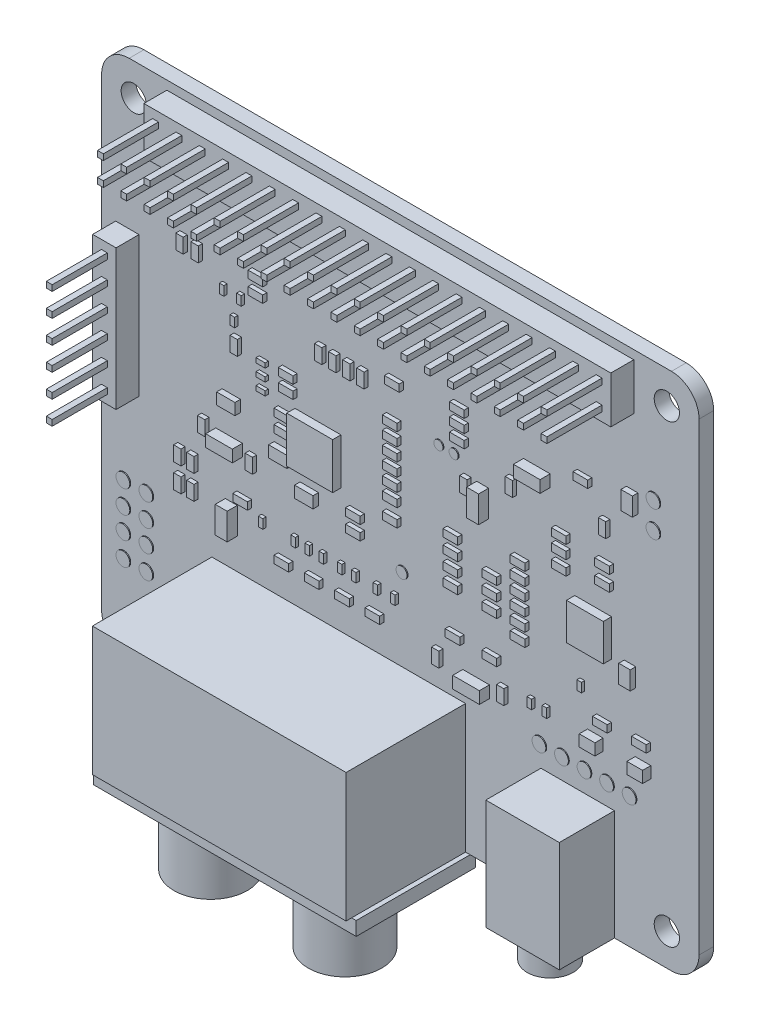
SolidWorks part; units mm, degrees
ref_plane "Front Plane" through (0, 0, 0) normal (0, 0, 1) x (1, 0, 0)
ref_plane "Top Plane" through (0, 0, 0) normal (0, 1, 0) x (1, 0, 0)
ref_plane "Right Plane" through (0, 0, 0) normal (1, 0, 0) x (0, 0, -1)
sketch "Sketch1" plane through (0, 0, 0) normal (0, 0, 1) x (1, 0, 0)
  line L0 (3, 0) -> (62, 0)
  line L1 (65, 3) -> (65, 53.5)
  line L2 (62, 56.5) -> (3, 56.5)
  line L3 (0, 53.5) -> (0, 3)
  arc A0 (62, 0) -> (65, 3) centre (62, 3) ccw
  arc A1 (65, 53.5) -> (62, 56.5) centre (62, 53.5) ccw
  arc A2 (3, 56.5) -> (0, 53.5) centre (3, 53.5) ccw
  arc A3 (0, 3) -> (3, 0) centre (3, 3) ccw
extrude "PCB" add sketch "Sketch1" along normal blind 1.6
ref_plane "Plane_z1_6" through (0, 0, 1.6) normal (0, 0, 1) x (1, 0, 0)
sketch "Sketch2" plane through (0, 0, 1.6) normal (0, 0, 1) x (1, 0, 0)
  line L1 (7.1, 50.46) -> (57.9, 50.46)
  line L2 (7.1, 50.46) -> (7.1, 55.54)
  line L3 (7.1, 55.54) -> (57.9, 55.54)
  line L4 (57.9, 50.46) -> (57.9, 55.54)
  line L6 (1.53, 25.18) -> (4.07, 25.18)
  line L7 (1.53, 25.18) -> (1.53, 40.42)
  line L8 (1.53, 40.42) -> (4.07, 40.42)
  line L9 (4.07, 25.18) -> (4.07, 40.42)
extrude "Header_Blocks" add sketch "Sketch2" along normal blind 2.5
ref_plane "Plane_z4_1" through (0, 0, 4.1) normal (0, 0, 1) x (1, 0, 0)
sketch "Sketch3" plane through (0, 0, 4.1) normal (0, 0, 1) x (1, 0, 0)
  line L1 (8.05, 51.41) -> (8.69, 51.41)
  line L2 (8.05, 51.41) -> (8.05, 52.05)
  line L3 (8.05, 52.05) -> (8.69, 52.05)
  line L4 (8.69, 51.41) -> (8.69, 52.05)
  line L6 (8.05, 53.95) -> (8.69, 53.95)
  line L7 (8.05, 53.95) -> (8.05, 54.59)
  line L8 (8.05, 54.59) -> (8.69, 54.59)
  line L9 (8.69, 53.95) -> (8.69, 54.59)
  line L11 (10.59, 51.41) -> (11.23, 51.41)
  line L12 (10.59, 51.41) -> (10.59, 52.05)
  line L13 (10.59, 52.05) -> (11.23, 52.05)
  line L14 (11.23, 51.41) -> (11.23, 52.05)
  line L16 (10.59, 53.95) -> (11.23, 53.95)
  line L17 (10.59, 53.95) -> (10.59, 54.59)
  line L18 (10.59, 54.59) -> (11.23, 54.59)
  line L19 (11.23, 53.95) -> (11.23, 54.59)
  line L21 (13.13, 51.41) -> (13.77, 51.41)
  line L22 (13.13, 51.41) -> (13.13, 52.05)
  line L23 (13.13, 52.05) -> (13.77, 52.05)
  line L24 (13.77, 51.41) -> (13.77, 52.05)
  line L26 (13.13, 53.95) -> (13.77, 53.95)
  line L27 (13.13, 53.95) -> (13.13, 54.59)
  line L28 (13.13, 54.59) -> (13.77, 54.59)
  line L29 (13.77, 53.95) -> (13.77, 54.59)
  line L31 (15.67, 51.41) -> (16.31, 51.41)
  line L32 (15.67, 51.41) -> (15.67, 52.05)
  line L33 (15.67, 52.05) -> (16.31, 52.05)
  line L34 (16.31, 51.41) -> (16.31, 52.05)
  line L36 (15.67, 53.95) -> (16.31, 53.95)
  line L37 (15.67, 53.95) -> (15.67, 54.59)
  line L38 (15.67, 54.59) -> (16.31, 54.59)
  line L39 (16.31, 53.95) -> (16.31, 54.59)
  line L41 (18.21, 51.41) -> (18.85, 51.41)
  line L42 (18.21, 51.41) -> (18.21, 52.05)
  line L43 (18.21, 52.05) -> (18.85, 52.05)
  line L44 (18.85, 51.41) -> (18.85, 52.05)
  line L46 (18.21, 53.95) -> (18.85, 53.95)
  line L47 (18.21, 53.95) -> (18.21, 54.59)
  line L48 (18.21, 54.59) -> (18.85, 54.59)
  line L49 (18.85, 53.95) -> (18.85, 54.59)
  line L51 (20.75, 51.41) -> (21.39, 51.41)
  line L52 (20.75, 51.41) -> (20.75, 52.05)
  line L53 (20.75, 52.05) -> (21.39, 52.05)
  line L54 (21.39, 51.41) -> (21.39, 52.05)
  line L56 (20.75, 53.95) -> (21.39, 53.95)
  line L57 (20.75, 53.95) -> (20.75, 54.59)
  line L58 (20.75, 54.59) -> (21.39, 54.59)
  line L59 (21.39, 53.95) -> (21.39, 54.59)
  line L61 (23.29, 51.41) -> (23.93, 51.41)
  line L62 (23.29, 51.41) -> (23.29, 52.05)
  line L63 (23.29, 52.05) -> (23.93, 52.05)
  line L64 (23.93, 51.41) -> (23.93, 52.05)
  line L66 (23.29, 53.95) -> (23.93, 53.95)
  line L67 (23.29, 53.95) -> (23.29, 54.59)
  line L68 (23.29, 54.59) -> (23.93, 54.59)
  line L69 (23.93, 53.95) -> (23.93, 54.59)
  line L71 (25.83, 51.41) -> (26.47, 51.41)
  line L72 (25.83, 51.41) -> (25.83, 52.05)
  line L73 (25.83, 52.05) -> (26.47, 52.05)
  line L74 (26.47, 51.41) -> (26.47, 52.05)
  line L76 (25.83, 53.95) -> (26.47, 53.95)
  line L77 (25.83, 53.95) -> (25.83, 54.59)
  line L78 (25.83, 54.59) -> (26.47, 54.59)
  line L79 (26.47, 53.95) -> (26.47, 54.59)
  line L81 (28.37, 51.41) -> (29.01, 51.41)
  line L82 (28.37, 51.41) -> (28.37, 52.05)
  line L83 (28.37, 52.05) -> (29.01, 52.05)
  line L84 (29.01, 51.41) -> (29.01, 52.05)
  line L86 (28.37, 53.95) -> (29.01, 53.95)
  line L87 (28.37, 53.95) -> (28.37, 54.59)
  line L88 (28.37, 54.59) -> (29.01, 54.59)
  line L89 (29.01, 53.95) -> (29.01, 54.59)
  line L91 (30.91, 51.41) -> (31.55, 51.41)
  line L92 (30.91, 51.41) -> (30.91, 52.05)
  line L93 (30.91, 52.05) -> (31.55, 52.05)
  line L94 (31.55, 51.41) -> (31.55, 52.05)
  line L96 (30.91, 53.95) -> (31.55, 53.95)
  line L97 (30.91, 53.95) -> (30.91, 54.59)
  line L98 (30.91, 54.59) -> (31.55, 54.59)
  line L99 (31.55, 53.95) -> (31.55, 54.59)
  line L101 (33.45, 51.41) -> (34.09, 51.41)
  line L102 (33.45, 51.41) -> (33.45, 52.05)
  line L103 (33.45, 52.05) -> (34.09, 52.05)
  line L104 (34.09, 51.41) -> (34.09, 52.05)
  line L106 (33.45, 53.95) -> (34.09, 53.95)
  line L107 (33.45, 53.95) -> (33.45, 54.59)
  line L108 (33.45, 54.59) -> (34.09, 54.59)
  line L109 (34.09, 53.95) -> (34.09, 54.59)
  line L111 (35.99, 51.41) -> (36.63, 51.41)
  line L112 (35.99, 51.41) -> (35.99, 52.05)
  line L113 (35.99, 52.05) -> (36.63, 52.05)
  line L114 (36.63, 51.41) -> (36.63, 52.05)
  line L116 (35.99, 53.95) -> (36.63, 53.95)
  line L117 (35.99, 53.95) -> (35.99, 54.59)
  line L118 (35.99, 54.59) -> (36.63, 54.59)
  line L119 (36.63, 53.95) -> (36.63, 54.59)
  line L121 (38.53, 51.41) -> (39.17, 51.41)
  line L122 (38.53, 51.41) -> (38.53, 52.05)
  line L123 (38.53, 52.05) -> (39.17, 52.05)
  line L124 (39.17, 51.41) -> (39.17, 52.05)
  line L126 (38.53, 53.95) -> (39.17, 53.95)
  line L127 (38.53, 53.95) -> (38.53, 54.59)
  line L128 (38.53, 54.59) -> (39.17, 54.59)
  line L129 (39.17, 53.95) -> (39.17, 54.59)
  line L131 (41.07, 51.41) -> (41.71, 51.41)
  line L132 (41.07, 51.41) -> (41.07, 52.05)
  line L133 (41.07, 52.05) -> (41.71, 52.05)
  line L134 (41.71, 51.41) -> (41.71, 52.05)
  line L136 (41.07, 53.95) -> (41.71, 53.95)
  line L137 (41.07, 53.95) -> (41.07, 54.59)
  line L138 (41.07, 54.59) -> (41.71, 54.59)
  line L139 (41.71, 53.95) -> (41.71, 54.59)
  line L141 (43.61, 51.41) -> (44.25, 51.41)
  line L142 (43.61, 51.41) -> (43.61, 52.05)
  line L143 (43.61, 52.05) -> (44.25, 52.05)
  line L144 (44.25, 51.41) -> (44.25, 52.05)
  line L146 (43.61, 53.95) -> (44.25, 53.95)
  line L147 (43.61, 53.95) -> (43.61, 54.59)
  line L148 (43.61, 54.59) -> (44.25, 54.59)
  line L149 (44.25, 53.95) -> (44.25, 54.59)
  line L151 (46.15, 51.41) -> (46.79, 51.41)
  line L152 (46.15, 51.41) -> (46.15, 52.05)
  line L153 (46.15, 52.05) -> (46.79, 52.05)
  line L154 (46.79, 51.41) -> (46.79, 52.05)
  line L156 (46.15, 53.95) -> (46.79, 53.95)
  line L157 (46.15, 53.95) -> (46.15, 54.59)
  line L158 (46.15, 54.59) -> (46.79, 54.59)
  line L159 (46.79, 53.95) -> (46.79, 54.59)
  line L161 (48.69, 51.41) -> (49.33, 51.41)
  line L162 (48.69, 51.41) -> (48.69, 52.05)
  line L163 (48.69, 52.05) -> (49.33, 52.05)
  line L164 (49.33, 51.41) -> (49.33, 52.05)
  line L166 (48.69, 53.95) -> (49.33, 53.95)
  line L167 (48.69, 53.95) -> (48.69, 54.59)
  line L168 (48.69, 54.59) -> (49.33, 54.59)
  line L169 (49.33, 53.95) -> (49.33, 54.59)
  line L171 (51.23, 51.41) -> (51.87, 51.41)
  line L172 (51.23, 51.41) -> (51.23, 52.05)
  line L173 (51.23, 52.05) -> (51.87, 52.05)
  line L174 (51.87, 51.41) -> (51.87, 52.05)
  line L176 (51.23, 53.95) -> (51.87, 53.95)
  line L177 (51.23, 53.95) -> (51.23, 54.59)
  line L178 (51.23, 54.59) -> (51.87, 54.59)
  line L179 (51.87, 53.95) -> (51.87, 54.59)
  line L181 (53.77, 51.41) -> (54.41, 51.41)
  line L182 (53.77, 51.41) -> (53.77, 52.05)
  line L183 (53.77, 52.05) -> (54.41, 52.05)
  line L184 (54.41, 51.41) -> (54.41, 52.05)
  line L186 (53.77, 53.95) -> (54.41, 53.95)
  line L187 (53.77, 53.95) -> (53.77, 54.59)
  line L188 (53.77, 54.59) -> (54.41, 54.59)
  line L189 (54.41, 53.95) -> (54.41, 54.59)
  line L191 (56.31, 51.41) -> (56.95, 51.41)
  line L192 (56.31, 51.41) -> (56.31, 52.05)
  line L193 (56.31, 52.05) -> (56.95, 52.05)
  line L194 (56.95, 51.41) -> (56.95, 52.05)
  line L196 (56.31, 53.95) -> (56.95, 53.95)
  line L197 (56.31, 53.95) -> (56.31, 54.59)
  line L198 (56.31, 54.59) -> (56.95, 54.59)
  line L199 (56.95, 53.95) -> (56.95, 54.59)
  line L201 (2.48, 26.13) -> (3.12, 26.13)
  line L202 (2.48, 26.13) -> (2.48, 26.77)
  line L203 (2.48, 26.77) -> (3.12, 26.77)
  line L204 (3.12, 26.13) -> (3.12, 26.77)
  line L206 (2.48, 28.67) -> (3.12, 28.67)
  line L207 (2.48, 28.67) -> (2.48, 29.31)
  line L208 (2.48, 29.31) -> (3.12, 29.31)
  line L209 (3.12, 28.67) -> (3.12, 29.31)
  line L211 (2.48, 31.21) -> (3.12, 31.21)
  line L212 (2.48, 31.21) -> (2.48, 31.85)
  line L213 (2.48, 31.85) -> (3.12, 31.85)
  line L214 (3.12, 31.21) -> (3.12, 31.85)
  line L216 (2.48, 33.75) -> (3.12, 33.75)
  line L217 (2.48, 33.75) -> (2.48, 34.39)
  line L218 (2.48, 34.39) -> (3.12, 34.39)
  line L219 (3.12, 33.75) -> (3.12, 34.39)
  line L221 (2.48, 36.29) -> (3.12, 36.29)
  line L222 (2.48, 36.29) -> (2.48, 36.93)
  line L223 (2.48, 36.93) -> (3.12, 36.93)
  line L224 (3.12, 36.29) -> (3.12, 36.93)
  line L226 (2.48, 38.83) -> (3.12, 38.83)
  line L227 (2.48, 38.83) -> (2.48, 39.47)
  line L228 (2.48, 39.47) -> (3.12, 39.47)
  line L229 (3.12, 38.83) -> (3.12, 39.47)
extrude "Header_Pins" add sketch "Sketch3" along normal blind 6
sketch "Sketch4" plane through (0, 0, 1.6) normal (0, 0, 1) x (1, 0, 0)
  line L1 (17.1462, 35.0397) -> (18.1462, 35.0397)
  line L2 (17.1462, 35.0397) -> (17.1462, 35.5397)
  line L3 (17.1462, 35.5397) -> (18.1462, 35.5397)
  line L4 (18.1462, 35.0397) -> (18.1462, 35.5397)
  line L6 (17.1462, 33.7251) -> (18.1462, 33.7251)
  line L7 (17.1462, 33.7251) -> (17.1462, 34.2251)
  line L8 (17.1462, 34.2251) -> (18.1462, 34.2251)
  line L9 (18.1462, 33.7251) -> (18.1462, 34.2251)
  line L11 (17.1462, 32.4104) -> (18.1462, 32.4104)
  line L12 (17.1462, 32.4104) -> (17.1462, 32.9104)
  line L13 (17.1462, 32.9104) -> (18.1462, 32.9104)
  line L14 (18.1462, 32.4104) -> (18.1462, 32.9104)
  line L16 (13.1523, 39.5701) -> (13.6523, 39.5701)
  line L17 (13.1523, 39.5701) -> (13.1523, 40.5701)
  line L18 (13.1523, 40.5701) -> (13.6523, 40.5701)
  line L19 (13.6523, 39.5701) -> (13.6523, 40.5701)
  line L21 (15.0385, 39.5701) -> (15.5385, 39.5701)
  line L22 (15.0385, 39.5701) -> (15.0385, 40.5701)
  line L23 (15.0385, 40.5701) -> (15.5385, 40.5701)
  line L24 (15.5385, 39.5701) -> (15.5385, 40.5701)
  line L26 (14.3312, 37.1799) -> (14.8312, 37.1799)
  line L27 (14.3312, 37.1799) -> (14.3312, 38.1799)
  line L28 (14.3312, 38.1799) -> (14.8312, 38.1799)
  line L29 (14.8312, 37.1799) -> (14.8312, 38.1799)
  line L31 (17.3962, 19.7314) -> (17.8962, 19.7314)
  line L32 (17.3962, 19.7314) -> (17.3962, 20.7314)
  line L33 (17.3962, 20.7314) -> (17.8962, 20.7314)
  line L34 (17.8962, 19.7314) -> (17.8962, 20.7314)
  line L36 (20.9328, 19.7314) -> (21.4328, 19.7314)
  line L37 (20.9328, 19.7314) -> (20.9328, 20.7314)
  line L38 (20.9328, 20.7314) -> (21.4328, 20.7314)
  line L39 (21.4328, 19.7314) -> (21.4328, 20.7314)
  line L41 (22.4653, 19.7314) -> (22.9653, 19.7314)
  line L42 (22.4653, 19.7314) -> (22.4653, 20.7314)
  line L43 (22.4653, 20.7314) -> (22.9653, 20.7314)
  line L44 (22.9653, 19.7314) -> (22.9653, 20.7314)
  line L46 (23.9978, 19.7314) -> (24.4978, 19.7314)
  line L47 (23.9978, 19.7314) -> (23.9978, 20.7314)
  line L48 (23.9978, 20.7314) -> (24.4978, 20.7314)
  line L49 (24.4978, 19.7314) -> (24.4978, 20.7314)
  line L51 (26.0018, 19.7314) -> (26.5018, 19.7314)
  line L52 (26.0018, 19.7314) -> (26.0018, 20.7314)
  line L53 (26.0018, 20.7314) -> (26.5018, 20.7314)
  line L54 (26.5018, 19.7314) -> (26.5018, 20.7314)
  line L56 (27.5343, 19.7314) -> (28.0343, 19.7314)
  line L57 (27.5343, 19.7314) -> (27.5343, 20.7314)
  line L58 (27.5343, 20.7314) -> (28.0343, 20.7314)
  line L59 (28.0343, 19.7314) -> (28.0343, 20.7314)
  line L61 (29.892, 19.7314) -> (30.392, 19.7314)
  line L62 (29.892, 19.7314) -> (29.892, 20.7314)
  line L63 (29.892, 20.7314) -> (30.392, 20.7314)
  line L64 (30.392, 19.7314) -> (30.392, 20.7314)
  line L66 (31.7782, 19.7314) -> (32.2782, 19.7314)
  line L67 (31.7782, 19.7314) -> (31.7782, 20.7314)
  line L68 (31.7782, 20.7314) -> (32.2782, 20.7314)
  line L69 (32.2782, 19.7314) -> (32.2782, 20.7314)
  line L71 (46.6317, 17.3412) -> (47.1317, 17.3412)
  line L72 (46.6317, 17.3412) -> (46.6317, 18.3412)
  line L73 (46.6317, 18.3412) -> (47.1317, 18.3412)
  line L74 (47.1317, 17.3412) -> (47.1317, 18.3412)
  line L76 (48.2821, 17.3412) -> (48.7821, 17.3412)
  line L77 (48.2821, 17.3412) -> (48.2821, 18.3412)
  line L78 (48.2821, 18.3412) -> (48.7821, 18.3412)
  line L79 (48.7821, 17.3412) -> (48.7821, 18.3412)
  line L81 (52.0544, 21.6436) -> (52.5544, 21.6436)
  line L82 (52.0544, 21.6436) -> (52.0544, 22.6436)
  line L83 (52.0544, 22.6436) -> (52.5544, 22.6436)
  line L84 (52.5544, 21.6436) -> (52.5544, 22.6436)
extrude "SMD_h0_35" add sketch "Sketch4" along normal blind 0.35
sketch "Sketch5" plane through (0, 0, 1.6) normal (0, 0, 1) x (1, 0, 0)
  line L1 (23.612, 38.553) -> (24.412, 38.553)
  line L2 (23.612, 38.553) -> (23.612, 40.153)
  line L3 (23.612, 40.153) -> (24.412, 40.153)
  line L4 (24.412, 38.553) -> (24.412, 40.153)
  line L6 (25.1445, 38.553) -> (25.9445, 38.553)
  line L7 (25.1445, 38.553) -> (25.1445, 40.153)
  line L8 (25.1445, 40.153) -> (25.9445, 40.153)
  line L9 (25.9445, 38.553) -> (25.9445, 40.153)
  line L11 (26.677, 38.553) -> (27.477, 38.553)
  line L12 (26.677, 38.553) -> (26.677, 40.153)
  line L13 (26.677, 40.153) -> (27.477, 40.153)
  line L14 (27.477, 38.553) -> (27.477, 40.153)
  line L16 (28.2095, 38.553) -> (29.0095, 38.553)
  line L17 (28.2095, 38.553) -> (28.2095, 40.153)
  line L18 (28.2095, 40.153) -> (29.0095, 40.153)
  line L19 (29.0095, 38.553) -> (29.0095, 40.153)
  line L21 (31.2282, 40.1481) -> (32.8282, 40.1481)
  line L22 (31.2282, 40.1481) -> (31.2282, 40.9481)
  line L23 (31.2282, 40.9481) -> (32.8282, 40.9481)
  line L24 (32.8282, 40.1481) -> (32.8282, 40.9481)
  line L26 (16.3747, 42.6578) -> (17.9747, 42.6578)
  line L27 (16.3747, 42.6578) -> (16.3747, 43.4578)
  line L28 (16.3747, 43.4578) -> (17.9747, 43.4578)
  line L29 (17.9747, 42.6578) -> (17.9747, 43.4578)
  line L31 (16.3747, 41.1042) -> (17.9747, 41.1042)
  line L32 (16.3747, 41.1042) -> (16.3747, 41.9042)
  line L33 (16.3747, 41.9042) -> (17.9747, 41.9042)
  line L34 (17.9747, 41.1042) -> (17.9747, 41.9042)
  line L36 (38.3013, 41.2237) -> (39.9013, 41.2237)
  line L37 (38.3013, 41.2237) -> (38.3013, 42.0237)
  line L38 (38.3013, 42.0237) -> (39.9013, 42.0237)
  line L39 (39.9013, 41.2237) -> (39.9013, 42.0237)
  line L41 (38.3013, 39.7896) -> (39.9013, 39.7896)
  line L42 (38.3013, 39.7896) -> (38.3013, 40.5896)
  line L43 (38.3013, 40.5896) -> (39.9013, 40.5896)
  line L44 (39.9013, 39.7896) -> (39.9013, 40.5896)
  line L46 (38.3013, 38.3555) -> (39.9013, 38.3555)
  line L47 (38.3013, 38.3555) -> (38.3013, 39.1555)
  line L48 (38.3013, 39.1555) -> (39.9013, 39.1555)
  line L49 (39.9013, 38.3555) -> (39.9013, 39.1555)
  line L51 (30.9924, 36.3238) -> (32.5924, 36.3238)
  line L52 (30.9924, 36.3238) -> (30.9924, 37.1238)
  line L53 (30.9924, 37.1238) -> (32.5924, 37.1238)
  line L54 (32.5924, 36.3238) -> (32.5924, 37.1238)
  line L56 (30.9924, 34.8897) -> (32.5924, 34.8897)
  line L57 (30.9924, 34.8897) -> (30.9924, 35.6897)
  line L58 (30.9924, 35.6897) -> (32.5924, 35.6897)
  line L59 (32.5924, 34.8897) -> (32.5924, 35.6897)
  line L61 (30.9924, 33.4555) -> (32.5924, 33.4555)
  line L62 (30.9924, 33.4555) -> (30.9924, 34.2555)
  line L63 (30.9924, 34.2555) -> (32.5924, 34.2555)
  line L64 (32.5924, 33.4555) -> (32.5924, 34.2555)
  line L66 (30.9924, 32.0214) -> (32.5924, 32.0214)
  line L67 (30.9924, 32.0214) -> (30.9924, 32.8214)
  line L68 (30.9924, 32.8214) -> (32.5924, 32.8214)
  line L69 (32.5924, 32.0214) -> (32.5924, 32.8214)
  line L71 (30.9924, 30.5873) -> (32.5924, 30.5873)
  line L72 (30.9924, 30.5873) -> (30.9924, 31.3873)
  line L73 (30.9924, 31.3873) -> (32.5924, 31.3873)
  line L74 (32.5924, 30.5873) -> (32.5924, 31.3873)
  line L76 (30.9924, 29.1532) -> (32.5924, 29.1532)
  line L77 (30.9924, 29.1532) -> (30.9924, 29.9532)
  line L78 (30.9924, 29.9532) -> (32.5924, 29.9532)
  line L79 (32.5924, 29.1532) -> (32.5924, 29.9532)
  line L81 (30.9924, 27.241) -> (32.5924, 27.241)
  line L82 (30.9924, 27.241) -> (30.9924, 28.041)
  line L83 (30.9924, 28.041) -> (32.5924, 28.041)
  line L84 (32.5924, 27.241) -> (32.5924, 28.041)
  line L86 (19.6754, 35.1287) -> (21.2754, 35.1287)
  line L87 (19.6754, 35.1287) -> (19.6754, 35.9287)
  line L88 (19.6754, 35.9287) -> (21.2754, 35.9287)
  line L89 (21.2754, 35.1287) -> (21.2754, 35.9287)
  line L91 (19.6754, 33.6946) -> (21.2754, 33.6946)
  line L92 (19.6754, 33.6946) -> (19.6754, 34.4946)
  line L93 (19.6754, 34.4946) -> (21.2754, 34.4946)
  line L94 (21.2754, 33.6946) -> (21.2754, 34.4946)
  line L96 (19.2039, 31.0653) -> (20.8039, 31.0653)
  line L97 (19.2039, 31.0653) -> (19.2039, 31.8653)
  line L98 (19.2039, 31.8653) -> (20.8039, 31.8653)
  line L99 (20.8039, 31.0653) -> (20.8039, 31.8653)
  line L101 (19.2039, 29.5117) -> (20.8039, 29.5117)
  line L102 (19.2039, 29.5117) -> (19.2039, 30.3117)
  line L103 (19.2039, 30.3117) -> (20.8039, 30.3117)
  line L104 (20.8039, 29.5117) -> (20.8039, 30.3117)
  line L106 (26.9843, 25.5679) -> (28.5843, 25.5679)
  line L107 (26.9843, 25.5679) -> (26.9843, 26.3679)
  line L108 (26.9843, 26.3679) -> (28.5843, 26.3679)
  line L109 (28.5843, 25.5679) -> (28.5843, 26.3679)
  line L111 (26.9843, 24.0143) -> (28.5843, 24.0143)
  line L112 (26.9843, 24.0143) -> (26.9843, 24.8143)
  line L113 (26.9843, 24.8143) -> (28.5843, 24.8143)
  line L114 (28.5843, 24.0143) -> (28.5843, 24.8143)
  line L116 (37.594, 28.9142) -> (39.194, 28.9142)
  line L117 (37.594, 28.9142) -> (37.594, 29.7142)
  line L118 (37.594, 29.7142) -> (39.194, 29.7142)
  line L119 (39.194, 28.9142) -> (39.194, 29.7142)
  line L121 (37.594, 27.3605) -> (39.194, 27.3605)
  line L122 (37.594, 27.3605) -> (37.594, 28.1605)
  line L123 (37.594, 28.1605) -> (39.194, 28.1605)
  line L124 (39.194, 27.3605) -> (39.194, 28.1605)
  line L126 (37.594, 25.8069) -> (39.194, 25.8069)
  line L127 (37.594, 25.8069) -> (37.594, 26.6069)
  line L128 (37.594, 26.6069) -> (39.194, 26.6069)
  line L129 (39.194, 25.8069) -> (39.194, 26.6069)
  line L131 (37.594, 24.2533) -> (39.194, 24.2533)
  line L132 (37.594, 24.2533) -> (37.594, 25.0533)
  line L133 (37.594, 25.0533) -> (39.194, 25.0533)
  line L134 (39.194, 24.2533) -> (39.194, 25.0533)
  line L136 (41.8378, 27.241) -> (43.4378, 27.241)
  line L137 (41.8378, 27.241) -> (41.8378, 28.041)
  line L138 (41.8378, 28.041) -> (43.4378, 28.041)
  line L139 (43.4378, 27.241) -> (43.4378, 28.041)
  line L141 (41.8378, 25.6874) -> (43.4378, 25.6874)
  line L142 (41.8378, 25.6874) -> (41.8378, 26.4874)
  line L143 (41.8378, 26.4874) -> (43.4378, 26.4874)
  line L144 (43.4378, 25.6874) -> (43.4378, 26.4874)
  line L146 (41.8378, 24.1338) -> (43.4378, 24.1338)
  line L147 (41.8378, 24.1338) -> (41.8378, 24.9338)
  line L148 (41.8378, 24.9338) -> (43.4378, 24.9338)
  line L149 (43.4378, 24.1338) -> (43.4378, 24.9338)
  line L151 (44.9028, 30.1093) -> (46.5028, 30.1093)
  line L152 (44.9028, 30.1093) -> (44.9028, 30.9093)
  line L153 (44.9028, 30.9093) -> (46.5028, 30.9093)
  line L154 (46.5028, 30.1093) -> (46.5028, 30.9093)
  line L156 (44.9028, 28.6751) -> (46.5028, 28.6751)
  line L157 (44.9028, 28.6751) -> (44.9028, 29.4751)
  line L158 (44.9028, 29.4751) -> (46.5028, 29.4751)
  line L159 (46.5028, 28.6751) -> (46.5028, 29.4751)
  line L161 (44.9028, 27.241) -> (46.5028, 27.241)
  line L162 (44.9028, 27.241) -> (44.9028, 28.041)
  line L163 (44.9028, 28.041) -> (46.5028, 28.041)
  line L164 (46.5028, 27.241) -> (46.5028, 28.041)
  line L166 (44.9028, 25.8069) -> (46.5028, 25.8069)
  line L167 (44.9028, 25.8069) -> (44.9028, 26.6069)
  line L168 (44.9028, 26.6069) -> (46.5028, 26.6069)
  line L169 (46.5028, 25.8069) -> (46.5028, 26.6069)
  line L171 (44.9028, 24.3728) -> (46.5028, 24.3728)
  line L172 (44.9028, 24.3728) -> (44.9028, 25.1728)
  line L173 (44.9028, 25.1728) -> (46.5028, 25.1728)
  line L174 (46.5028, 24.3728) -> (46.5028, 25.1728)
  line L176 (44.9028, 22.9387) -> (46.5028, 22.9387)
  line L177 (44.9028, 22.9387) -> (44.9028, 23.7387)
  line L178 (44.9028, 23.7387) -> (46.5028, 23.7387)
  line L179 (46.5028, 22.9387) -> (46.5028, 23.7387)
  line L181 (49.3825, 34.8897) -> (50.9825, 34.8897)
  line L182 (49.3825, 34.8897) -> (49.3825, 35.6897)
  line L183 (49.3825, 35.6897) -> (50.9825, 35.6897)
  line L184 (50.9825, 34.8897) -> (50.9825, 35.6897)
  line L186 (49.3825, 33.4555) -> (50.9825, 33.4555)
  line L187 (49.3825, 33.4555) -> (49.3825, 34.2555)
  line L188 (49.3825, 34.2555) -> (50.9825, 34.2555)
  line L189 (50.9825, 33.4555) -> (50.9825, 34.2555)
  line L191 (49.3825, 31.9019) -> (50.9825, 31.9019)
  line L192 (49.3825, 31.9019) -> (49.3825, 32.7019)
  line L193 (49.3825, 32.7019) -> (50.9825, 32.7019)
  line L194 (50.9825, 31.9019) -> (50.9825, 32.7019)
  line L196 (54.4979, 37.5969) -> (55.2979, 37.5969)
  line L197 (54.4979, 37.5969) -> (54.4979, 39.1969)
  line L198 (54.4979, 39.1969) -> (55.2979, 39.1969)
  line L199 (55.2979, 37.5969) -> (55.2979, 39.1969)
  line L201 (54.0979, 34.4116) -> (55.6979, 34.4116)
  line L202 (54.0979, 34.4116) -> (54.0979, 35.2116)
  line L203 (54.0979, 35.2116) -> (55.6979, 35.2116)
  line L204 (55.6979, 34.4116) -> (55.6979, 35.2116)
  line L206 (54.0979, 32.7385) -> (55.6979, 32.7385)
  line L207 (54.0979, 32.7385) -> (54.0979, 33.5385)
  line L208 (54.0979, 33.5385) -> (55.6979, 33.5385)
  line L209 (55.6979, 32.7385) -> (55.6979, 33.5385)
  line L211 (51.7402, 41.3432) -> (53.3402, 41.3432)
  line L212 (51.7402, 41.3432) -> (51.7402, 42.1432)
  line L213 (51.7402, 42.1432) -> (53.3402, 42.1432)
  line L214 (53.3402, 41.3432) -> (53.3402, 42.1432)
  line L216 (39.4086, 34.0116) -> (40.2086, 34.0116)
  line L217 (39.4086, 34.0116) -> (39.4086, 35.6116)
  line L218 (39.4086, 35.6116) -> (40.2086, 35.6116)
  line L219 (40.2086, 34.0116) -> (40.2086, 35.6116)
  line L221 (44.3598, 36.4018) -> (45.1598, 36.4018)
  line L222 (44.3598, 36.4018) -> (44.3598, 38.0018)
  line L223 (44.3598, 38.0018) -> (45.1598, 38.0018)
  line L224 (45.1598, 36.4018) -> (45.1598, 38.0018)
  line L226 (19.2039, 17.2022) -> (20.8039, 17.2022)
  line L227 (19.2039, 17.2022) -> (19.2039, 18.0022)
  line L228 (19.2039, 18.0022) -> (20.8039, 18.0022)
  line L229 (20.8039, 17.2022) -> (20.8039, 18.0022)
  line L231 (22.5047, 17.2022) -> (24.1047, 17.2022)
  line L232 (22.5047, 17.2022) -> (22.5047, 18.0022)
  line L233 (22.5047, 18.0022) -> (24.1047, 18.0022)
  line L234 (24.1047, 17.2022) -> (24.1047, 18.0022)
  line L236 (25.8055, 17.2022) -> (27.4055, 17.2022)
  line L237 (25.8055, 17.2022) -> (25.8055, 18.0022)
  line L238 (25.8055, 18.0022) -> (27.4055, 18.0022)
  line L239 (27.4055, 17.2022) -> (27.4055, 18.0022)
  line L241 (29.1062, 17.2022) -> (30.7062, 17.2022)
  line L242 (29.1062, 17.2022) -> (29.1062, 18.0022)
  line L243 (29.1062, 18.0022) -> (30.7062, 18.0022)
  line L244 (30.7062, 17.2022) -> (30.7062, 18.0022)
  line L246 (8.2869, 21.3436) -> (9.0869, 21.3436)
  line L247 (8.2869, 21.3436) -> (8.2869, 22.9436)
  line L248 (8.2869, 22.9436) -> (9.0869, 22.9436)
  line L249 (9.0869, 21.3436) -> (9.0869, 22.9436)
  line L251 (9.7016, 21.3436) -> (10.5016, 21.3436)
  line L252 (9.7016, 21.3436) -> (9.7016, 22.9436)
  line L253 (9.7016, 22.9436) -> (10.5016, 22.9436)
  line L254 (10.5016, 21.3436) -> (10.5016, 22.9436)
  line L256 (8.2869, 18.7143) -> (9.0869, 18.7143)
  line L257 (8.2869, 18.7143) -> (8.2869, 20.3143)
  line L258 (8.2869, 20.3143) -> (9.0869, 20.3143)
  line L259 (9.0869, 18.7143) -> (9.0869, 20.3143)
  line L261 (9.7016, 18.7143) -> (10.5016, 18.7143)
  line L262 (9.7016, 18.7143) -> (9.7016, 20.3143)
  line L263 (9.7016, 20.3143) -> (10.5016, 20.3143)
  line L264 (10.5016, 18.7143) -> (10.5016, 20.3143)
  line L266 (14.7243, 20.7875) -> (16.3243, 20.7875)
  line L267 (14.7243, 20.7875) -> (14.7243, 21.5875)
  line L268 (14.7243, 21.5875) -> (16.3243, 21.5875)
  line L269 (16.3243, 20.7875) -> (16.3243, 21.5875)
  line L271 (16.0674, 24.4508) -> (16.8673, 24.4508)
  line L272 (16.0674, 24.4508) -> (16.0674, 26.0508)
  line L273 (16.0674, 26.0508) -> (16.8673, 26.0508)
  line L274 (16.8673, 24.4508) -> (16.8673, 26.0508)
  line L276 (10.8804, 25.4069) -> (11.6804, 25.4069)
  line L277 (10.8804, 25.4069) -> (10.8804, 27.0069)
  line L278 (10.8804, 27.0069) -> (11.6804, 27.0069)
  line L279 (11.6804, 25.4069) -> (11.6804, 27.0069)
  line L281 (8.5227, 41.4212) -> (9.3227, 41.4212)
  line L282 (8.5227, 41.4212) -> (8.5227, 43.0212)
  line L283 (8.5227, 43.0212) -> (9.3227, 43.0212)
  line L284 (9.3227, 41.4212) -> (9.3227, 43.0212)
  line L286 (10.1731, 41.4212) -> (10.9731, 41.4212)
  line L287 (10.1731, 41.4212) -> (10.1731, 43.0212)
  line L288 (10.1731, 43.0212) -> (10.9731, 43.0212)
  line L289 (10.9731, 41.4212) -> (10.9731, 43.0212)
  line L291 (14.417, 34.7287) -> (15.217, 34.7287)
  line L292 (14.417, 34.7287) -> (14.417, 36.3287)
  line L293 (14.417, 36.3287) -> (15.217, 36.3287)
  line L294 (15.217, 34.7287) -> (15.217, 36.3287)
  line L296 (41.8378, 19.5924) -> (43.4378, 19.5924)
  line L297 (41.8378, 19.5924) -> (41.8378, 20.3924)
  line L298 (41.8378, 20.3924) -> (43.4378, 20.3924)
  line L299 (43.4378, 19.5924) -> (43.4378, 20.3924)
  line L301 (37.8297, 19.5924) -> (39.4297, 19.5924)
  line L302 (37.8297, 19.5924) -> (37.8297, 20.3924)
  line L303 (37.8297, 20.3924) -> (39.4297, 20.3924)
  line L304 (39.4297, 19.5924) -> (39.4297, 20.3924)
  line L306 (36.3436, 16.3241) -> (37.1436, 16.3241)
  line L307 (36.3436, 16.3241) -> (36.3436, 17.9241)
  line L308 (36.3436, 17.9241) -> (37.1436, 17.9241)
  line L309 (37.1436, 16.3241) -> (37.1436, 17.9241)
  line L311 (43.4167, 16.3241) -> (44.2167, 16.3241)
  line L312 (43.4167, 16.3241) -> (43.4167, 17.9241)
  line L313 (43.4167, 17.9241) -> (44.2167, 17.9241)
  line L314 (44.2167, 16.3241) -> (44.2167, 17.9241)
  line L316 (53.8621, 19.3534) -> (55.4621, 19.3534)
  line L317 (53.8621, 19.3534) -> (53.8621, 20.1534)
  line L318 (53.8621, 20.1534) -> (55.4621, 20.1534)
  line L319 (55.4621, 19.3534) -> (55.4621, 20.1534)
  line L321 (58.106, 19.5924) -> (59.706, 19.5924)
  line L322 (58.106, 19.5924) -> (58.106, 20.3924)
  line L323 (58.106, 20.3924) -> (59.706, 20.3924)
  line L324 (59.706, 19.5924) -> (59.706, 20.3924)
extrude "SMD_h0_45" add sketch "Sketch5" along normal blind 0.45
sketch "Sketch6" plane through (0, 0, 1.6) normal (0, 0, 1) x (1, 0, 0)
  line L1 (21.5974, 24.6258) -> (23.5974, 24.6258)
  line L2 (21.5974, 24.6258) -> (21.5974, 25.8758)
  line L3 (21.5974, 25.8758) -> (23.5974, 25.8758)
  line L4 (23.5974, 24.6258) -> (23.5974, 25.8758)
  line L6 (18.7681, 27.016) -> (20.7681, 27.016)
  line L7 (18.7681, 27.016) -> (18.7681, 28.266)
  line L8 (18.7681, 28.266) -> (20.7681, 28.266)
  line L9 (20.7681, 27.016) -> (20.7681, 28.266)
  line L11 (13.1097, 29.1672) -> (15.1097, 29.1672)
  line L12 (13.1097, 29.1672) -> (13.1097, 30.4172)
  line L13 (13.1097, 30.4172) -> (15.1097, 30.4172)
  line L14 (15.1097, 29.1672) -> (15.1097, 30.4172)
  line L16 (57.1021, 41.2212) -> (58.3521, 41.2212)
  line L17 (57.1021, 41.2212) -> (57.1021, 43.2212)
  line L18 (57.1021, 43.2212) -> (58.3521, 43.2212)
  line L19 (58.3521, 41.2212) -> (58.3521, 43.2212)
  line L21 (56.8663, 24.7289) -> (58.1163, 24.7289)
  line L22 (56.8663, 24.7289) -> (56.8663, 26.7289)
  line L23 (56.8663, 26.7289) -> (58.1163, 26.7289)
  line L24 (58.1163, 24.7289) -> (58.1163, 26.7289)
extrude "SMD_h0_6" add sketch "Sketch6" along normal blind 0.6
sketch "Sketch7" plane through (0, 0, 1.6) normal (0, 0, 1) x (1, 0, 0)
  line L1 (21.0404, 27.5312) -> (26.0404, 27.5312)
  line L2 (21.0404, 27.5312) -> (21.0404, 32.5312)
  line L3 (21.0404, 32.5312) -> (26.0404, 32.5312)
  line L4 (26.0404, 27.5312) -> (26.0404, 32.5312)
  line L6 (51.4832, 26.1191) -> (55.4832, 26.1191)
  line L7 (51.4832, 26.1191) -> (51.4832, 30.1191)
  line L8 (51.4832, 30.1191) -> (55.4832, 30.1191)
  line L9 (55.4832, 26.1191) -> (55.4832, 30.1191)
  line L11 (52.869, 16.9772) -> (54.569, 16.9772)
  line L12 (52.869, 16.9772) -> (52.869, 18.2272)
  line L13 (52.869, 18.2272) -> (54.569, 18.2272)
  line L14 (54.569, 16.9772) -> (54.569, 18.2272)
  line L16 (58.056, 16.9772) -> (59.756, 16.9772)
  line L17 (58.056, 16.9772) -> (58.056, 18.2272)
  line L18 (58.056, 18.2272) -> (59.756, 18.2272)
  line L19 (59.756, 16.9772) -> (59.756, 18.2272)
extrude "SMD_h0_9" add sketch "Sketch7" along normal blind 0.9
sketch "Sketch8" plane through (0, 0, 1.6) normal (0, 0, 1) x (1, 0, 0)
  line L1 (45.9032, 38.942) -> (48.8032, 38.942)
  line L2 (45.9032, 38.942) -> (45.9032, 40.242)
  line L3 (45.9032, 40.242) -> (48.8032, 40.242)
  line L4 (48.8032, 38.942) -> (48.8032, 40.242)
  line L6 (40.809, 32.6446) -> (42.109, 32.6446)
  line L7 (40.809, 32.6446) -> (40.809, 35.5446)
  line L8 (40.809, 35.5446) -> (42.109, 35.5446)
  line L9 (42.109, 32.6446) -> (42.109, 35.5446)
  line L11 (13.4596, 17.3473) -> (14.7597, 17.3473)
  line L12 (13.4596, 17.3473) -> (13.4596, 20.2473)
  line L13 (13.4596, 20.2473) -> (14.7597, 20.2473)
  line L14 (14.7597, 17.3473) -> (14.7597, 20.2473)
  line L16 (12.4239, 25.0789) -> (15.3239, 25.0789)
  line L17 (12.4239, 25.0789) -> (12.4239, 26.3789)
  line L18 (12.4239, 26.3789) -> (15.3239, 26.3789)
  line L19 (15.3239, 25.0789) -> (15.3239, 26.3789)
  line L21 (39.3017, 15.7571) -> (42.2017, 15.7571)
  line L22 (39.3017, 15.7571) -> (39.3017, 17.0571)
  line L23 (39.3017, 17.0571) -> (42.2017, 17.0571)
  line L24 (42.2017, 15.7571) -> (42.2017, 17.0571)
extrude "SMD_h1_1" add sketch "Sketch8" along normal blind 1.1
sketch "Sketch9" plane through (0, 0, 1.6) normal (0, 0, 1) x (1, 0, 0)
  circle A0 centre (2.4155, 16.5027) radius 0.75
  circle A1 centre (2.4155, 14.0169) radius 0.75
  circle A2 centre (2.4155, 11.6267) radius 0.75
  circle A3 centre (2.4155, 9.0931) radius 0.75
  circle A4 centre (4.9146, 16.5027) radius 0.75
  circle A5 centre (4.9146, 14.0169) radius 0.75
  circle A6 centre (4.9146, 11.6267) radius 0.75
  circle A7 centre (4.9146, 9.0931) radius 0.75
  circle A8 centre (47.6833, 14.2559) radius 0.75
  circle A9 centre (50.1353, 14.2559) radius 0.75
  circle A10 centre (52.5873, 14.2559) radius 0.75
  circle A11 centre (55.0393, 14.2559) radius 0.75
  circle A12 centre (57.4913, 14.2559) radius 0.75
  circle A13 centre (60.0848, 43.4163) radius 0.75
  circle A14 centre (60.0848, 40.5481) radius 0.75
  circle A15 centre (32.7355, 22.9562) radius 0.6
  circle A16 centre (36.7436, 36.9628) radius 0.5
  circle A17 centre (38.394, 36.9628) radius 0.5
extrude "Pads" add sketch "Sketch9" along normal blind 0.1
sketch "Sketch10" plane through (0, 0, 1.6) normal (0, 0, 1) x (1, 0, 0)
  line L1 (12, 0) -> (39.6, 0)
  line L2 (12, 0) -> (12, 14)
  line L3 (12, 14) -> (39.6, 14)
  line L4 (39.6, 0) -> (39.6, 14)
extrude "RCA_Housing" add sketch "Sketch10" along normal blind 13
sketch "Sketch11" plane through (0, 0, 0) normal (0, 1, 0) x (1, 0, 0)
  line L1 (11.5, -1) -> (40.1, -1)
  line L2 (11.5, -1) -> (11.5, -14)
  line L3 (11.5, -14) -> (40.1, -14)
  line L4 (40.1, -1) -> (40.1, -14)
extrude "RCA_Plate" add sketch "Sketch11" against normal blind 1.5
sketch "Sketch12" plane through (0, 0, 0) normal (0, 1, 0) x (1, 0, 0)
  circle A0 centre (18.36, -8.1) radius 4
  circle A1 centre (32.98, -8.1) radius 4
extrude "RCA_Barrels" add sketch "Sketch12" against normal blind 9
sketch "Sketch13" plane through (0, 0, 1.6) normal (0, 0, 1) x (1, 0, 0)
  line L1 (47.8, 0) -> (55.8, 0)
  line L2 (47.8, 0) -> (47.8, 12)
  line L3 (47.8, 12) -> (55.8, 12)
  line L4 (55.8, 0) -> (55.8, 12)
extrude "Jack_Body" add sketch "Sketch13" along normal blind 6
sketch "Sketch14" plane through (0, 0, 0) normal (0, 1, 0) x (1, 0, 0)
  circle A0 centre (51.8, -4.6) radius 2.5
extrude "Jack_Nose" add sketch "Sketch14" against normal blind 2.5
sketch "Sketch15" plane through (0, 0, 0) normal (0, 1, 0) x (1, 0, 0)
  circle A0 centre (18.36, -8.1) radius 2.5
  circle A1 centre (32.98, -8.1) radius 2.5
extrude "RCA_Bores" cut sketch "Sketch15" along normal blind 9
sketch "Sketch16" plane through (0, 0, 0) normal (0, 1, 0) x (1, 0, 0)
  circle A0 centre (51.8, -4.6) radius 1.75
extrude "Jack_Bore" cut sketch "Sketch16" along normal blind 2.5
sketch "Sketch17" plane through (0, 0, 0) normal (0, 0, 1) x (1, 0, 0)
  circle A0 centre (3.5, 3.5) radius 1.375
  circle A1 centre (3.5, 53) radius 1.375
  circle A2 centre (61.5, 3.5) radius 1.375
  circle A3 centre (61.5, 53) radius 1.375
extrude "Mount_Holes" cut sketch "Sketch17" against normal through all and the other way through all
equation "\"pcb_l\" = 65mm"
equation "\"pcb_w\" = 56.5mm"
equation "\"pcb_t\" = 1.6mm"
equation "\"pcb_r\" = 3mm"
equation "\"hole_d\" = 2.75mm"
equation "\"hole_inset\" = 3.5mm"
equation "\"hdr_pitch\" = 2.54mm"
equation "\"hdr_block_h\" = 2.5mm"
equation "\"hdr_pin\" = 0.64mm"
equation "\"hdr_pin_h\" = 6mm"
equation "\"p7_x\" = 2.8mm"
equation "\"p7_y\" = 32.8mm"
equation "\"p7_n\" = 6mm"
equation "\"rca_x0\" = 12.0mm"
equation "\"rca_x1\" = 39.6mm"
equation "\"rca_d\" = 14mm"
equation "\"rca_h\" = 13mm"
equation "\"rca_plate_extra\" = 0.5mm"
equation "\"rca_plate_t\" = 1.5mm"
equation "\"rca_axis_h\" = 6.5mm"
equation "\"rca_bx1\" = 18.36mm"
equation "\"rca_bx2\" = 32.98mm"
equation "\"rca_barrel_d\" = 8mm"
equation "\"rca_barrel_out\" = 9mm"
equation "\"rca_bore_d\" = 5mm"
equation "\"jack_x\" = 51.8mm"
equation "\"jack_w\" = 8mm"
equation "\"jack_d\" = 12mm"
equation "\"jack_h\" = 6mm"
equation "\"jack_nose_d\" = 5mm"
equation "\"jack_nose_out\" = 2.5mm"
equation "\"jack_bore_d\" = 3.5mm"
equation "\"D1@PCB\" = \"pcb_t\""
equation "\"D1@RCA_Barrels\" = \"rca_barrel_out\""
